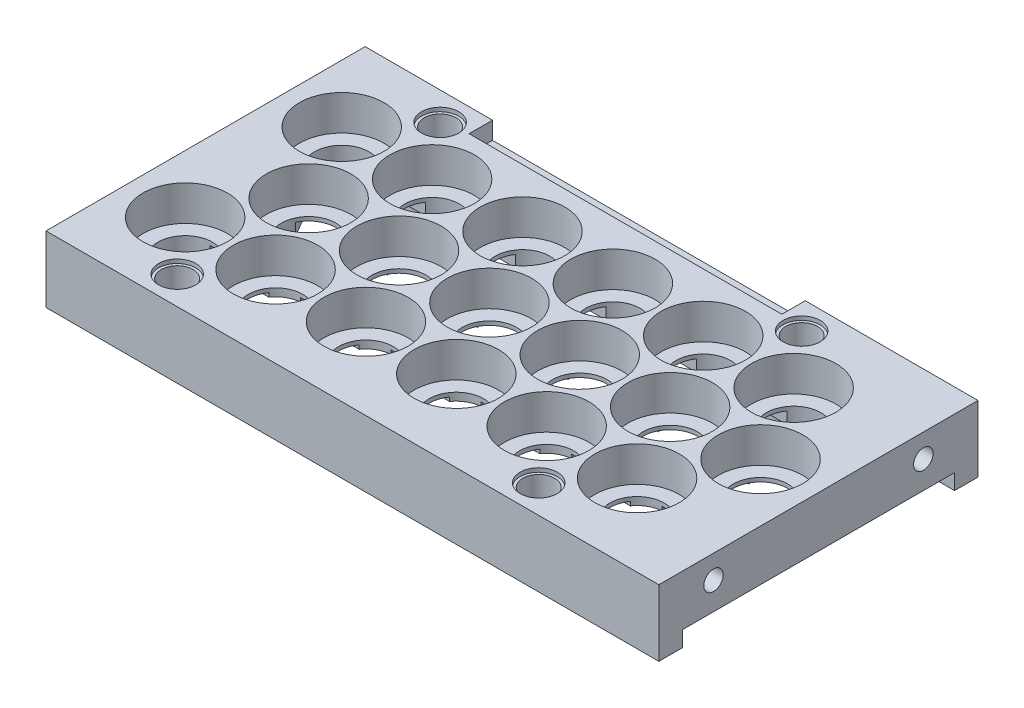
SolidWorks part; units mm, degrees
ref_plane "Front Plane" through (0, 0, 0) normal (0, 0, 1) x (1, 0, 0)
ref_plane "Top Plane" through (0, 0, 0) normal (0, 1, 0) x (1, 0, 0)
ref_plane "Right Plane" through (0, 0, 0) normal (1, 0, 0) x (0, 0, -1)
sketch "Sketch1" plane through (0, 0, 0) normal (0, 1, 0) x (1, 0, 0)
  line L0 (0, 0) -> (11.575, -20.0485) construction
  line L1 (11.575, -20.0485) -> (0, -40.097) construction
  line L2 (0, 0) -> (11.575, 0) construction
  line L3 (11.575, 0) -> (11.575, -20.0485) construction
  line L4 (11.575, -20.0485) -> (11.575, -40.097) construction
  line L5 (11.575, -40.097) -> (0, -40.097) construction
  line L6 (0, 0) -> (23.15, 0) construction
  line L7 (0, 0) -> (23.15, 0) construction
  line L8 (-14.825, -60.922) -> (142.15, -60.922)
  line L9 (-14.825, -60.922) -> (-14.825, 20.825)
  line L10 (-14.825, 20.825) -> (142.15, 20.825)
  line L11 (142.15, -60.922) -> (142.15, 20.825)
  circle A0 centre (0, 0) radius 10.825
  circle A1 centre (11.575, -20.0485) radius 10.825
  circle A2 centre (0, -40.097) radius 10.825
  circle A3 centre (23.15, 0) radius 10.825
  circle A4 centre (34.725, -20.0485) radius 10.825
  circle A5 centre (23.15, -40.097) radius 10.825
  circle A6 centre (46.3, 0) radius 10.825
  circle A7 centre (57.875, -20.0485) radius 10.825
  circle A8 centre (46.3, -40.097) radius 10.825
  circle A9 centre (69.45, 0) radius 10.825
  circle A10 centre (81.025, -20.0485) radius 10.825
  circle A11 centre (69.45, -40.097) radius 10.825
  circle A12 centre (92.6, 0) radius 10.825
  circle A13 centre (104.175, -20.0485) radius 10.825
  circle A14 centre (92.6, -40.097) radius 10.825
  circle A15 centre (115.75, 0) radius 10.825
  circle A16 centre (127.325, -20.0485) radius 10.825
  circle A17 centre (115.75, -40.097) radius 10.825
  circle A18 centre (0, 0) radius 7
  circle A19 centre (11.575, -20.0485) radius 7
  circle A20 centre (0, -40.097) radius 7
  circle A21 centre (23.15, 0) radius 7
  circle A22 centre (34.725, -20.0485) radius 7
  circle A23 centre (23.15, -40.097) radius 7
  circle A24 centre (46.3, 0) radius 7
  circle A25 centre (57.875, -20.0485) radius 7
  circle A26 centre (46.3, -40.097) radius 7
  circle A27 centre (69.45, 0) radius 7
  circle A28 centre (81.025, -20.0485) radius 7
  circle A29 centre (69.45, -40.097) radius 7
  circle A30 centre (92.6, 0) radius 7
  circle A31 centre (104.175, -20.0485) radius 7
  circle A32 centre (92.6, -40.097) radius 7
  circle A33 centre (115.75, 0) radius 7
  circle A34 centre (127.325, -20.0485) radius 7
  circle A35 centre (115.75, -40.097) radius 7
  dimension "D3" = 21.65
  dimension "D11" = 14
  dimension "D1" = 60
  dimension "D2" = 60
  dimension "D4" = 1.5
  dimension "D6" = 23.15
  dimension "D7" = 4
  dimension "D8" = 4
  dimension "D9" = 10
  dimension "D10" = 10
  dimension "D13" = 23.15
  dimension "D5" = 6
  dimension "D12" = 6
extrude "Boss-Extrude2" add sketch "Sketch1" along normal blind 11 contours L8 L11 L10 L9 A17 A16 A15 A14 A13 A12 A11 A10 A9 A8 A7 A6 A5 A4 A3 A2 A1 A0 region at (-13.0551, 0, 20.0485)
extrude "Boss-Extrude3" add sketch "Sketch1<3>" along normal blind 2 contours A0 A18 | A3 A21 | A6 A24 | A9 A27 | A12 A30 | A15 A33 | A1 A19 | A4 A22 | A7 A25 | A10 A28 | A13 A31 | A16 A34 | A17 A35 | A14 A32 | A11 A29 | A8 A26 | A5 A23 | A2 A20 region at (-10.5188, 0, 0) region at (1.0562, 0, 20.0485) region at (-10.5188, 0, 40.097) region at (12.6312, 0, 0) region at (24.2062, 0, 20.0485) region at (12.6312, 0, 40.097) region at (35.7812, 0, 0) region at (47.3562, 0, 20.0485) region at (35.7812, 0, 40.097) region at (58.9312, 0, 0) region at (70.5062, 0, 20.0485) region at (58.9312, 0, 40.097) region at (82.0812, 0, 0) region at (93.6562, 0, 20.0485) region at (82.0812, 0, 40.097) region at (105.2312, 0, 0) region at (116.8062, 0, 20.0485) region at (105.2312, 0, 40.097)
sketch "Sketch1<3>" plane through (0, 0, 0) normal (0, 1, 0) x (1, 0, 0) same geometry as "Sketch1"
sketch "Sketch2" plane through (0, 0, 0) normal (0, -1, 0) x (1, 0, 0)
  line L0 (0, 40.097) -> (11.575, 20.0485) construction
  line L1 (3.4641, 42.097) -> (15.0391, 22.0485)
  line L2 (-3.4641, 38.097) -> (8.1109, 18.0485)
  line L3 (11.575, 20.0485) -> (0, 0) construction
  line L4 (15.0391, 18.0485) -> (3.4641, -2)
  line L5 (8.1109, 22.0485) -> (-3.4641, 2)
  line L6 (19.6859, 38.097) -> (31.2609, 18.0485)
  line L7 (26.6141, 42.097) -> (38.1891, 22.0485)
  line L8 (31.2609, 22.0485) -> (19.6859, 2)
  line L9 (38.1891, 18.0485) -> (26.6141, -2)
  line L10 (23.15, 40.097) -> (34.725, 20.0485) construction
  line L11 (34.725, 20.0485) -> (23.15, 0) construction
  line L12 (42.8359, 38.097) -> (54.4109, 18.0485)
  line L13 (49.7641, 42.097) -> (61.3391, 22.0485)
  line L14 (54.4109, 22.0485) -> (42.8359, 2)
  line L15 (61.3391, 18.0485) -> (49.7641, -2)
  line L16 (46.3, 40.097) -> (57.875, 20.0485) construction
  line L17 (57.875, 20.0485) -> (46.3, 0) construction
  line L18 (65.9859, 38.097) -> (77.5609, 18.0485)
  line L19 (72.9141, 42.097) -> (84.4891, 22.0485)
  line L20 (77.5609, 22.0485) -> (65.9859, 2)
  line L21 (84.4891, 18.0485) -> (72.9141, -2)
  line L22 (69.45, 40.097) -> (81.025, 20.0485) construction
  line L23 (81.025, 20.0485) -> (69.45, 0) construction
  line L24 (89.1359, 38.097) -> (100.7109, 18.0485)
  line L25 (96.0641, 42.097) -> (107.6391, 22.0485)
  line L26 (100.7109, 22.0485) -> (89.1359, 2)
  line L27 (107.6391, 18.0485) -> (96.0641, -2)
  line L28 (92.6, 40.097) -> (104.175, 20.0485) construction
  line L29 (104.175, 20.0485) -> (92.6, 0) construction
  line L30 (112.2859, 38.097) -> (123.8609, 18.0485)
  line L31 (119.2141, 42.097) -> (130.7891, 22.0485)
  line L32 (123.8609, 22.0485) -> (112.2859, 2)
  line L33 (130.7891, 18.0485) -> (119.2141, -2)
  line L34 (115.75, 40.097) -> (127.325, 20.0485) construction
  line L35 (127.325, 20.0485) -> (115.75, 0) construction
  line L36 (-3.4641, 38.097) -> (19.6859, 38.097) construction
  line L37 (0, 40.097) -> (115.75, 40.097) construction
  line L38 (0, 44.097) -> (115.75, 44.097)
  line L39 (0, 36.097) -> (115.75, 36.097)
  line L40 (11.575, 20.0485) -> (127.325, 20.0485) construction
  line L41 (11.575, 24.0485) -> (127.325, 24.0485)
  line L42 (11.575, 16.0485) -> (127.325, 16.0485)
  line L43 (0, 0) -> (115.75, 0) construction
  line L44 (0, 4) -> (115.75, 4)
  line L45 (0, -4) -> (115.75, -4)
  arc A0 (3.4641, 42.097) -> (-3.4641, 38.097) centre (0, 40.097) ccw
  arc A1 (8.1109, 18.0485) -> (15.0391, 22.0485) centre (11.575, 20.0485) ccw
  arc A2 (15.0391, 18.0485) -> (8.1109, 22.0485) centre (11.575, 20.0485) ccw
  arc A3 (-3.4641, 2) -> (3.4641, -2) centre (0, 0) ccw
  arc A4 (26.6141, 42.097) -> (19.6859, 38.097) centre (23.15, 40.097) ccw
  arc A5 (31.2609, 18.0485) -> (38.1891, 22.0485) centre (34.725, 20.0485) ccw
  arc A6 (38.1891, 18.0485) -> (31.2609, 22.0485) centre (34.725, 20.0485) ccw
  arc A7 (19.6859, 2) -> (26.6141, -2) centre (23.15, 0) ccw
  arc A8 (49.7641, 42.097) -> (42.8359, 38.097) centre (46.3, 40.097) ccw
  arc A9 (54.4109, 18.0485) -> (61.3391, 22.0485) centre (57.875, 20.0485) ccw
  arc A10 (61.3391, 18.0485) -> (54.4109, 22.0485) centre (57.875, 20.0485) ccw
  arc A11 (42.8359, 2) -> (49.7641, -2) centre (46.3, 0) ccw
  arc A12 (72.9141, 42.097) -> (65.9859, 38.097) centre (69.45, 40.097) ccw
  arc A13 (77.5609, 18.0485) -> (84.4891, 22.0485) centre (81.025, 20.0485) ccw
  arc A14 (84.4891, 18.0485) -> (77.5609, 22.0485) centre (81.025, 20.0485) ccw
  arc A15 (65.9859, 2) -> (72.9141, -2) centre (69.45, 0) ccw
  arc A16 (96.0641, 42.097) -> (89.1359, 38.097) centre (92.6, 40.097) ccw
  arc A17 (100.7109, 18.0485) -> (107.6391, 22.0485) centre (104.175, 20.0485) ccw
  arc A18 (107.6391, 18.0485) -> (100.7109, 22.0485) centre (104.175, 20.0485) ccw
  arc A19 (89.1359, 2) -> (96.0641, -2) centre (92.6, 0) ccw
  arc A20 (119.2141, 42.097) -> (112.2859, 38.097) centre (115.75, 40.097) ccw
  arc A21 (123.8609, 18.0485) -> (130.7891, 22.0485) centre (127.325, 20.0485) ccw
  arc A22 (130.7891, 18.0485) -> (123.8609, 22.0485) centre (127.325, 20.0485) ccw
  arc A23 (112.2859, 2) -> (119.2141, -2) centre (115.75, 0) ccw
  arc A24 (0, 44.097) -> (0, 36.097) centre (0, 40.097) ccw
  arc A25 (115.75, 36.097) -> (115.75, 44.097) centre (115.75, 40.097) ccw
  arc A26 (11.575, 24.0485) -> (11.575, 16.0485) centre (11.575, 20.0485) ccw
  arc A27 (127.325, 16.0485) -> (127.325, 24.0485) centre (127.325, 20.0485) ccw
  arc A28 (0, 4) -> (0, -4) centre (0, 0) ccw
  arc A29 (115.75, -4) -> (115.75, 4) centre (115.75, 0) ccw
  point P3 (5.7875, 30.0727)
  point P8 (5.7875, 10.0242)
  point P18 (28.9375, 30.0727)
  point P25 (28.9375, 10.0242)
  point P34 (52.0875, 30.0727)
  point P39 (52.0875, 10.0242)
  point P48 (75.2375, 30.0727)
  point P53 (75.2375, 10.0242)
  point P62 (98.3875, 30.0727)
  point P67 (98.3875, 10.0242)
  point P76 (121.5375, 30.0727)
  point P81 (121.5375, 10.0242)
  point P91 (57.875, 40.097)
  point P96 (69.45, 20.0485)
  point P103 (57.875, 0)
  circle M62 centre (0, 0) radius 7
  circle M63 centre (23.15, 0) radius 7
  circle M64 centre (46.3, 0) radius 7
  circle M65 centre (69.45, 0) radius 7
  circle M66 centre (92.6, 0) radius 7
  circle M67 centre (115.75, 0) radius 7
  circle M68 centre (11.575, 20.0485) radius 7
  circle M69 centre (34.725, 20.0485) radius 7
  circle M70 centre (57.875, 20.0485) radius 7
  circle M71 centre (81.025, 20.0485) radius 7
  circle M72 centre (104.175, 20.0485) radius 7
  circle M73 centre (127.325, 20.0485) radius 7
  circle M74 centre (115.75, 40.097) radius 7
  circle M75 centre (92.6, 40.097) radius 7
  circle M76 centre (69.45, 40.097) radius 7
  circle M77 centre (46.3, 40.097) radius 7
  circle M78 centre (23.15, 40.097) radius 7
  circle M79 centre (0, 40.097) radius 7
  dimension "D1" = 8
  dimension "D3" = 23.15
  dimension "D4" = 8
  dimension "D5" = 8
  dimension "D6" = 8
extrude "Cut-Extrude1" cut sketch "Sketch2" against normal blind 1 contours L1 L39 L38 M78 M79 | L7 L39 L38 M77 M78 | L39 L2 L1 M79 M68 | L42 L8 L6 L41 M68 M69 | L6 L41 L7 L39 M69 M78 | L12 L41 L13 L39 M70 M77 | L13 L39 L38 M76 M77 | L18 L41 L19 L39 M71 M76 | L19 L39 L38 M75 M76 | L24 L41 L25 L39 M72 M75 | L25 L39 L38 M74 M75 | L30 L41 L31 M73 M74 | L42 L32 L30 L41 M72 M73 | L42 L26 L24 L41 M71 M72 | L42 L20 L18 L41 M70 M71 | L42 L14 L12 L41 M69 M70 | L45 L44 L4 M62 M63 | L44 L4 L5 M62 M68 | L45 L44 L9 M63 M64 | L45 L44 L15 M64 M65 | L45 L44 L21 M65 M66 | L45 L44 L27 M66 M67 | L44 L27 L42 L26 M66 M72 | L42 L32 L33 M67 M73 | L44 L21 L42 L20 M65 M71 | L44 L15 L42 L14 M64 M70 | L39 L13 M77 | L39 L25 M75 | L39 L19 M76 | L41 L6 M69 | L44 L4 M62 | L44 L15 M64 | L44 L21 M65 | L44 L27 M66 | L41 L30 M73 | L32 L42 M73 | L41 L24 M72 | L26 L42 M72 | L41 L18 M71 | L20 L42 M71 | L41 L12 M70 | L14 L42 M70 | L44 L9 L42 L8 M63 M69 | L8 L42 M69 | L39 L7 M78 | L39 L1 M79 | L44 A29 L45 A28 region at (11.6138, 0, 40.1242) region at (6.3461, 0, 36.4331) region at (5.7834, 0, 30.0255) region at (23.0718, 0, 20.0485) region at (28.9375, 0, 30.0727) region at (34.7638, 0, 40.1242) region at (28.3789, 0, 23.7124) region at (5.7834, 0, 10.0715) region at (29.4961, 0, 36.4331) region at (57.9138, 0, 40.1242) region at (28.3789, 0, 16.3846) region at (28.9375, 0, 10.0242) region at (6.3461, 0, 3.6639) region at (11.6138, 0, -0.0272) region at (52.0875, 0, 30.0727) region at (46.2218, 0, 20.0485) region at (52.6461, 0, 36.4331) region at (81.0638, 0, 40.1242) region at (51.5289, 0, 23.7124) region at (34.7638, 0, -0.0272) region at (75.2375, 0, 30.0727) region at (75.7961, 0, 36.4331) region at (104.2138, 0, 40.1242) region at (74.6789, 0, 23.7124) region at (69.3718, 0, 20.0485) region at (51.5289, 0, 16.3846) region at (52.0875, 0, 10.0242) region at (57.9138, 0, -0.0272) region at (98.3875, 0, 30.0727) region at (98.9461, 0, 36.4331) region at (97.8289, 0, 23.7124) region at (92.5218, 0, 20.0485) region at (74.6789, 0, 16.3846) region at (52.6461, 0, 3.6639) region at (81.0638, 0, -0.0272) region at (121.5416, 0, 30.12) region at (75.2375, 0, 10.0242) region at (120.9789, 0, 23.7124) region at (115.6718, 0, 20.0485) region at (97.8289, 0, 16.3846) region at (75.7961, 0, 3.6639) region at (104.2138, 0, -0.0272) region at (98.3875, 0, 10.0242) region at (121.5416, 0, 9.977) region at (120.9789, 0, 16.3846) region at (98.9461, 0, 3.6639)
sketch "Sketch9" plane through (0, 11, 0) normal (0, 1, 0) x (1, 0, 0)
  line L0 (11.575, -60.922) -> (11.575, 20.825)
  line L1 (-14.825, 20.825) -> (142.15, 20.825) construction
  line L2 (104.175, 20.825) -> (104.175, -60.922)
  line L3 (-14.825, -60.922) -> (142.15, -60.922) construction
  circle A0 centre (11.575, 13.625) radius 4.0767
  circle A1 centre (11.575, -53.722) radius 4.0767
  circle A2 centre (104.175, -53.722) radius 4.0767
  circle A3 centre (104.175, 13.625) radius 4.0767
  point P0 (11.575, 13.625)
  point P7 (11.575, -20.0485)
  point P15 (104.175, -20.0485)
  point P20 (104.175, 13.625)
  point P21 (104.175, -53.722)
  point P22 (11.575, -53.722)
  dimension "D5" = 8.1534
  dimension "D1" = 7.2
  dimension "D4" = 7.2
extrude "Cut-Extrude3" cut sketch "Sketch9" against normal up to next contours A2 | A1 | A0 | A3
sketch "Sketch10" plane through (0, 11, 0) normal (0, 1, 0) x (1, 0, 0)
  circle A0 centre (11.575, 13.625) radius 4.7625
  circle A1 centre (104.175, 13.625) radius 4.7625
  circle A2 centre (104.175, -53.722) radius 4.7625
  circle A3 centre (11.575, -53.722) radius 4.7625
  dimension "D1" = 9.525
extrude "Cut-Extrude4" cut sketch "Sketch10" against normal blind 1
sketch "Sketch13" plane through (0, 0, 0) normal (0, -1, 0) x (1, 0, 0)
  line L0 (142.15, 60.922) -> (142.15, -20.825) construction
  line L5 (3.575, 53.722) -> (3.575, 60.922)
  line L8 (-14.825, 60.922) -> (142.15, 60.922) construction
  line L9 (3.575, 60.922) -> (19.575, 60.922)
  line L10 (19.575, 60.922) -> (19.575, 53.722)
  line L12 (57.875, 20.0485) -> (57.875, -20.825) construction
  line L13 (-14.825, -20.825) -> (142.15, -20.825) construction
  line L14 (11.575, 20.0485) -> (127.325, 20.0485) construction
  line L16 (96.175, 60.922) -> (96.175, 53.722)
  line L17 (112.175, 60.922) -> (96.175, 60.922)
  line L18 (112.175, 53.722) -> (112.175, 60.922)
  line L19 (-14.825, 60.922) -> (142.15, 60.922)
  line L20 (-14.825, 60.922) -> (-14.825, 54.922)
  line L21 (-14.825, 54.922) -> (142.15, 54.922)
  line L22 (142.15, 60.922) -> (142.15, 54.922)
  line L23 (142.15, -20.825) -> (142.15, -14.825)
  line L24 (-14.825, -14.825) -> (142.15, -14.825)
  line L25 (-14.825, -20.825) -> (-14.825, -14.825)
  line L26 (-14.825, -20.825) -> (142.15, -20.825)
  line L27 (112.175, -13.625) -> (112.175, -20.825)
  line L28 (112.175, -20.825) -> (96.175, -20.825)
  line L29 (96.175, -20.825) -> (96.175, -13.625)
  line L32 (19.575, -20.825) -> (19.575, -13.625)
  line L33 (3.575, -20.825) -> (19.575, -20.825)
  line L34 (3.575, -13.625) -> (3.575, -20.825)
  circle A4 centre (11.575, 53.722) radius 6.5
  circle A5 centre (11.575, 53.722) radius 8
  circle A6 centre (104.175, 53.722) radius 8
  circle A7 centre (104.175, 53.722) radius 6.5
  circle A8 centre (104.175, -13.625) radius 6.5
  circle A9 centre (104.175, -13.625) radius 8
  circle A10 centre (11.575, -13.625) radius 8
  circle A11 centre (11.575, -13.625) radius 6.5
  line M15 (142.15, 60.922) -> (-14.825, 60.922)
  line M16 (-14.825, 60.922) -> (-14.825, -20.825)
  line M17 (-14.825, -20.825) -> (142.15, -20.825)
  line M18 (142.15, -20.825) -> (142.15, 60.922)
  dimension "D1" = 13
  dimension "D2" = 16
  dimension "D3" = 6
extrude "Boss-Extrude7" add sketch "Sketch13" along normal blind 6 contours L21 L5 M16 M15 | A5 L5 L21 M15 | A5 L21 L10 M15 | L10 L21 L16 M15 | L21 A5 L19 A4 | A5 L21 A4 | L21 A6 L16 M15 | L21 A7 A6 L19 | L21 A7 A6 | A6 L21 L18 M15 | L18 L21 M18 M15 | A9 L24 L29 L26 | L28 A9 L24 A8 | A9 L26 L27 L24 | L24 L27 L26 M18 | L32 L26 L29 L24 | L24 A9 A8 | L34 L24 M16 M17 | L26 A10 L24 L34 | L24 A11 A10 | L24 A11 A10 L33 | L24 A10 L26 L32 region at (3.7817, 0, 54.3098) region at (-5.625, 0, 57.922) region at (4.8282, 0, 59.2567) region at (5.2714, 0, 58.3681) region at (18.3218, 0, 59.2567) region at (57.875, 0, 57.922) region at (-5.625, 0, -17.825) region at (97.4282, 0, 59.2567) region at (4.8282, 0, -19.1597) region at (96.3817, 0, 54.3098) region at (97.8714, 0, 58.3681) region at (3.7817, 0, -14.2128) region at (4.4261, 0, -14.9942) region at (110.9218, 0, 59.2567) region at (127.1625, 0, 57.922) region at (18.3218, 0, -19.1597) region at (57.875, 0, -17.825) region at (97.4282, 0, -19.1597) region at (127.1625, 0, -17.825) region at (96.3817, 0, -14.2128) region at (97.0261, 0, -14.9942) region at (110.9218, 0, -19.1597)
sketch "Sketch14" plane through (0, 0, 0) normal (0, -1, 0) x (1, 0, 0)
  line L2 (142.15, 54.922) -> (142.15, -14.825) construction
  line L4 (5.2386, 17.0736) -> (-0.5918, 6.9749) construction
  line L5 (5.7446, -4) -> (17.4054, -4) construction
  line L6 (28.8946, -4) -> (40.5554, -4) construction
  line L7 (52.0446, -4) -> (63.7054, -4) construction
  line L8 (75.1946, -4) -> (86.8554, -4) construction
  line L9 (98.3446, -4) -> (110.0054, -4) construction
  line L10 (127.9168, 13.0736) -> (122.0864, 2.9749) construction
  line L11 (122.0864, 37.122) -> (127.9168, 27.0234) construction
  line L12 (98.3446, 44.097) -> (110.0054, 44.097) construction
  line L13 (75.1946, 44.097) -> (86.8554, 44.097) construction
  line L14 (52.0446, 44.097) -> (63.7054, 44.097) construction
  line L15 (28.8946, 44.097) -> (40.5554, 44.097) construction
  line L16 (-0.5918, 33.122) -> (5.2386, 23.0234) construction
  line L17 (5.7446, 44.097) -> (17.4054, 44.097) construction
  line L20 (142.15, 54.922) -> (142.15, -14.825)
  line L22 (5.2386, 17.0736) -> (-0.5918, 6.9749)
  line L23 (5.7446, -4) -> (17.4054, -4)
  line L24 (28.8946, -4) -> (40.5554, -4)
  line L25 (52.0446, -4) -> (63.7054, -4)
  line L26 (75.1946, -4) -> (86.8554, -4)
  line L27 (98.3446, -4) -> (110.0054, -4)
  line L28 (127.9168, 13.0736) -> (122.0864, 2.9749)
  line L29 (122.0864, 37.122) -> (127.9168, 27.0234)
  line L30 (98.3446, 44.097) -> (110.0054, 44.097)
  line L31 (75.1946, 44.097) -> (86.8554, 44.097)
  line L32 (52.0446, 44.097) -> (63.7054, 44.097)
  line L33 (28.8946, 44.097) -> (40.5554, 44.097)
  line L34 (-0.5918, 33.122) -> (5.2386, 23.0234)
  line L35 (5.7446, 44.097) -> (17.4054, 44.097)
  line L36 (112.0845, -14.825) -> (142.15, -14.825) construction
  line L37 (19.4845, -14.825) -> (96.2655, -14.825) construction
  line L38 (-14.825, -14.825) -> (3.6655, -14.825) construction
  line L39 (-14.825, 54.922) -> (-14.825, -14.825) construction
  line L40 (112.0845, 54.922) -> (142.15, 54.922) construction
  line L41 (19.4845, 54.922) -> (96.2655, 54.922) construction
  line L42 (-14.825, 54.922) -> (3.6655, 54.922) construction
  line L43 (112.0845, -14.825) -> (142.15, -14.825)
  line L44 (19.4845, -14.825) -> (96.2655, -14.825)
  line L45 (-14.825, -14.825) -> (3.6655, -14.825)
  line L46 (-14.825, 54.922) -> (-14.825, -14.825)
  line L47 (112.0845, 54.922) -> (142.15, 54.922)
  line L48 (19.4845, 54.922) -> (96.2655, 54.922)
  line L49 (-14.825, 54.922) -> (3.6655, 54.922)
  arc A3 (5.2386, 23.0234) -> (5.2386, 17.0736) centre (11.575, 20.0485) ccw construction
  arc A4 (-0.5918, 6.9749) -> (5.7446, -4) centre (0, 0) ccw construction
  arc A5 (17.4054, -4) -> (28.8946, -4) centre (23.15, 0) ccw construction
  arc A6 (40.5554, -4) -> (52.0446, -4) centre (46.3, 0) ccw construction
  arc A7 (63.7054, -4) -> (75.1946, -4) centre (69.45, 0) ccw construction
  arc A8 (86.8554, -4) -> (98.3446, -4) centre (92.6, 0) ccw construction
  arc A9 (110.0054, -4) -> (122.0864, 2.9749) centre (115.75, 0) ccw construction
  arc A10 (127.9168, 13.0736) -> (127.9168, 27.0234) centre (127.325, 20.0485) ccw construction
  arc A11 (122.0864, 37.122) -> (110.0054, 44.097) centre (115.75, 40.097) ccw construction
  arc A12 (98.3446, 44.097) -> (86.8554, 44.097) centre (92.6, 40.097) ccw construction
  arc A13 (75.1946, 44.097) -> (63.7054, 44.097) centre (69.45, 40.097) ccw construction
  arc A14 (52.0446, 44.097) -> (40.5554, 44.097) centre (46.3, 40.097) ccw construction
  arc A16 (28.8946, 44.097) -> (17.4054, 44.097) centre (23.15, 40.097) ccw construction
  arc A17 (5.7446, 44.097) -> (-0.5918, 33.122) centre (0, 40.097) ccw construction
  arc A21 (5.2386, 23.0234) -> (5.2386, 17.0736) centre (11.575, 20.0485) ccw
  arc A22 (-0.5918, 6.9749) -> (5.7446, -4) centre (0, 0) ccw
  arc A23 (17.4054, -4) -> (28.8946, -4) centre (23.15, 0) ccw
  arc A24 (40.5554, -4) -> (52.0446, -4) centre (46.3, 0) ccw
  arc A25 (63.7054, -4) -> (75.1946, -4) centre (69.45, 0) ccw
  arc A26 (86.8554, -4) -> (98.3446, -4) centre (92.6, 0) ccw
  arc A27 (110.0054, -4) -> (122.0864, 2.9749) centre (115.75, 0) ccw
  arc A28 (127.9168, 13.0736) -> (127.9168, 27.0234) centre (127.325, 20.0485) ccw
  arc A29 (122.0864, 37.122) -> (110.0054, 44.097) centre (115.75, 40.097) ccw
  arc A30 (98.3446, 44.097) -> (86.8554, 44.097) centre (92.6, 40.097) ccw
  arc A31 (75.1946, 44.097) -> (63.7054, 44.097) centre (69.45, 40.097) ccw
  arc A32 (52.0446, 44.097) -> (40.5554, 44.097) centre (46.3, 40.097) ccw
  arc A34 (28.8946, 44.097) -> (17.4054, 44.097) centre (23.15, 40.097) ccw
  arc A35 (5.7446, 44.097) -> (-0.5918, 33.122) centre (0, 40.097) ccw
  arc A36 (112.0845, -14.825) -> (96.2655, -14.825) centre (104.175, -13.625) ccw construction
  arc A37 (19.4845, -14.825) -> (3.6655, -14.825) centre (11.575, -13.625) ccw construction
  arc A38 (96.2655, 54.922) -> (112.0845, 54.922) centre (104.175, 53.722) ccw construction
  arc A39 (3.6655, 54.922) -> (19.4845, 54.922) centre (11.575, 53.722) ccw construction
  arc A40 (112.0845, -14.825) -> (96.2655, -14.825) centre (104.175, -13.625) ccw
  arc A41 (19.4845, -14.825) -> (3.6655, -14.825) centre (11.575, -13.625) ccw
  arc A42 (96.2655, 54.922) -> (112.0845, 54.922) centre (104.175, 53.722) ccw
  arc A43 (3.6655, 54.922) -> (19.4845, 54.922) centre (11.575, 53.722) ccw
extrude "Boss-Extrude9" add sketch "Sketch14" along normal blind 2
sketch "Sketch16" plane through (0, 0, 0) normal (0, -1, 0) x (1, 0, 0)
  line L0 (17.4054, 36.097) -> (12.1668, 27.0234) construction
  line L1 (12.1668, 27.0234) -> (17.3196, 24.0485) construction
  line L2 (17.3196, 24.0485) -> (22.5582, 33.122) construction
  line L3 (22.5582, 33.122) -> (17.4054, 36.097) construction
  line L4 (14.7861, 31.5602) -> (19.9389, 28.5853) construction
  line L5 (15.5361, 32.8592) -> (20.6889, 29.8843)
  line L6 (14.0361, 30.2612) -> (19.1889, 27.2862)
  line L7 (11.575, 20.0485) -> (126.446, 20.0485) construction
  line L8 (40.5554, 36.097) -> (35.3168, 27.0234) construction
  line L9 (35.3168, 27.0234) -> (40.4696, 24.0485) construction
  line L10 (40.4696, 24.0485) -> (45.7082, 33.122) construction
  line L11 (45.7082, 33.122) -> (40.5554, 36.097) construction
  line L12 (37.9361, 31.5602) -> (43.0889, 28.5853) construction
  line L13 (38.6861, 32.8592) -> (43.8389, 29.8843)
  line L14 (37.1861, 30.2612) -> (42.3389, 27.2862)
  line L15 (63.7054, 36.097) -> (58.4668, 27.0234) construction
  line L16 (58.4668, 27.0234) -> (63.6196, 24.0485) construction
  line L17 (63.6196, 24.0485) -> (68.8582, 33.122) construction
  line L18 (68.8582, 33.122) -> (63.7054, 36.097) construction
  line L19 (61.0861, 31.5602) -> (66.2389, 28.5853) construction
  line L20 (61.8361, 32.8592) -> (66.9889, 29.8843)
  line L21 (60.3361, 30.2612) -> (65.4889, 27.2862)
  line L22 (86.8554, 36.097) -> (81.6168, 27.0234) construction
  line L23 (81.6168, 27.0234) -> (86.7696, 24.0485) construction
  line L24 (86.7696, 24.0485) -> (92.0082, 33.122) construction
  line L25 (92.0082, 33.122) -> (86.8554, 36.097) construction
  line L26 (84.2361, 31.5602) -> (89.3889, 28.5853) construction
  line L27 (84.9861, 32.8592) -> (90.1389, 29.8843)
  line L28 (83.4861, 30.2612) -> (88.6389, 27.2862)
  line L29 (110.0054, 36.097) -> (104.7668, 27.0234) construction
  line L30 (104.7668, 27.0234) -> (109.9196, 24.0485) construction
  line L31 (109.9196, 24.0485) -> (115.1582, 33.122) construction
  line L32 (115.1582, 33.122) -> (110.0054, 36.097) construction
  line L33 (107.3861, 31.5602) -> (112.5389, 28.5853) construction
  line L34 (108.1361, 32.8592) -> (113.2889, 29.8843)
  line L35 (106.6361, 30.2612) -> (111.7889, 27.2862)
  line L36 (14.7861, 8.5368) -> (19.9389, 11.5117) construction
  line L37 (15.5361, 7.2377) -> (20.6889, 10.2127)
  line L38 (14.0361, 9.8358) -> (19.1889, 12.8108)
  line L39 (37.9361, 8.5368) -> (43.0889, 11.5117) construction
  line L40 (38.6861, 7.2377) -> (43.8389, 10.2127)
  line L41 (37.1861, 9.8358) -> (42.3389, 12.8108)
  line L42 (61.0861, 8.5368) -> (66.2389, 11.5117) construction
  line L43 (61.8361, 7.2377) -> (66.9889, 10.2127)
  line L44 (60.3361, 9.8358) -> (65.4889, 12.8108)
  line L45 (84.2361, 8.5368) -> (89.3889, 11.5117) construction
  line L46 (84.9861, 7.2377) -> (90.1389, 10.2127)
  line L47 (83.4861, 9.8358) -> (88.6389, 12.8108)
  line L48 (107.3861, 8.5368) -> (112.5389, 11.5117) construction
  line L49 (108.1361, 7.2377) -> (113.2889, 10.2127)
  line L50 (106.6361, 9.8358) -> (111.7889, 12.8108)
  line L51 (115.1582, 6.9749) -> (110.0054, 4) construction
  line L52 (109.9196, 16.0485) -> (115.1582, 6.9749) construction
  line L53 (104.7668, 13.0736) -> (109.9196, 16.0485) construction
  line L54 (110.0054, 4) -> (104.7668, 13.0736) construction
  line L55 (92.0082, 6.9749) -> (86.8554, 4) construction
  line L56 (86.7696, 16.0485) -> (92.0082, 6.9749) construction
  line L57 (81.6168, 13.0736) -> (86.7696, 16.0485) construction
  line L58 (86.8554, 4) -> (81.6168, 13.0736) construction
  line L59 (68.8582, 6.9749) -> (63.7054, 4) construction
  line L60 (63.6196, 16.0485) -> (68.8582, 6.9749) construction
  line L61 (58.4668, 13.0736) -> (63.6196, 16.0485) construction
  line L62 (63.7054, 4) -> (58.4668, 13.0736) construction
  line L63 (45.7082, 6.9749) -> (40.5554, 4) construction
  line L64 (40.4696, 16.0485) -> (45.7082, 6.9749) construction
  line L65 (35.3168, 13.0736) -> (40.4696, 16.0485) construction
  line L66 (40.5554, 4) -> (35.3168, 13.0736) construction
  line L67 (22.5582, 6.9749) -> (17.4054, 4) construction
  line L68 (17.3196, 16.0485) -> (22.5582, 6.9749) construction
  line L69 (12.1668, 13.0736) -> (17.3196, 16.0485) construction
  line L70 (17.4054, 4) -> (12.1668, 13.0736) construction
  arc A0 (15.5361, 32.8592) -> (14.0361, 30.2612) centre (14.7861, 31.5602) ccw
  arc A1 (19.1889, 27.2862) -> (20.6889, 29.8843) centre (19.9389, 28.5853) ccw
  arc A2 (38.6861, 32.8592) -> (37.1861, 30.2612) centre (37.9361, 31.5602) ccw
  arc A3 (42.3389, 27.2862) -> (43.8389, 29.8843) centre (43.0889, 28.5853) ccw
  arc A4 (61.8361, 32.8592) -> (60.3361, 30.2612) centre (61.0861, 31.5602) ccw
  arc A5 (65.4889, 27.2862) -> (66.9889, 29.8843) centre (66.2389, 28.5853) ccw
  arc A6 (84.9861, 32.8592) -> (83.4861, 30.2612) centre (84.2361, 31.5602) ccw
  arc A7 (88.6389, 27.2862) -> (90.1389, 29.8843) centre (89.3889, 28.5853) ccw
  arc A8 (108.1361, 32.8592) -> (106.6361, 30.2612) centre (107.3861, 31.5602) ccw
  arc A9 (111.7889, 27.2862) -> (113.2889, 29.8843) centre (112.5389, 28.5853) ccw
  arc A10 (40.5554, 36.097) -> (45.7082, 33.122) centre (46.3, 40.097) ccw construction
  arc A11 (15.5361, 7.2377) -> (14.0361, 9.8358) centre (14.7861, 8.5368) cw
  arc A12 (19.1889, 12.8108) -> (20.6889, 10.2127) centre (19.9389, 11.5117) cw
  arc A13 (38.6861, 7.2377) -> (37.1861, 9.8358) centre (37.9361, 8.5368) cw
  arc A14 (42.3389, 12.8108) -> (43.8389, 10.2127) centre (43.0889, 11.5117) cw
  arc A15 (61.8361, 7.2377) -> (60.3361, 9.8358) centre (61.0861, 8.5368) cw
  arc A16 (65.4889, 12.8108) -> (66.9889, 10.2127) centre (66.2389, 11.5117) cw
  arc A17 (84.9861, 7.2377) -> (83.4861, 9.8358) centre (84.2361, 8.5368) cw
  arc A18 (88.6389, 12.8108) -> (90.1389, 10.2127) centre (89.3889, 11.5117) cw
  arc A19 (108.1361, 7.2377) -> (106.6361, 9.8358) centre (107.3861, 8.5368) cw
  arc A20 (111.7889, 12.8108) -> (113.2889, 10.2127) centre (112.5389, 11.5117) cw
  point P10 (17.3625, 30.0727)
  point P25 (40.5125, 30.0727)
  point P36 (63.6625, 30.0727)
  point P47 (86.8125, 30.0727)
  point P58 (109.9625, 30.0727)
  point P68 (17.3625, 10.0242)
  point P75 (40.5125, 10.0242)
  point P82 (63.6625, 10.0242)
  point P89 (86.8125, 10.0242)
  point P96 (109.9625, 10.0242)
  dimension "D1" = 1.5
  dimension "D2" = 5
extrude "Boss-Extrude10" add sketch "Sketch16" along normal blind 2
sketch "Sketch17" plane through (0, -2, 0) normal (0, -1, 0) x (-1, 0, 0)
  line L0 (-57.875, -44.097) -> (-57.875, -54.922) construction
  line L1 (-63.7054, -44.097) -> (-52.0446, -44.097) construction
  line L2 (-19.4845, -54.922) -> (-96.2655, -54.922) construction
  line L3 (-142.15, 14.825) -> (-142.15, -54.922) construction
  line L4 (14.825, -54.922) -> (14.825, 14.825) construction
  line L5 (10.825, -49.5095) -> (-57.875, -49.5095) construction
  line L6 (-57.875, -49.5095) -> (-132.15, -49.5095) construction
  line L7 (-127.325, -20.0485) -> (-11.575, -20.0485)
  line L8 (-57.875, 9.4125) -> (-132.15, 9.4125) construction
  line L9 (10.825, 9.4125) -> (-57.875, 9.4125) construction
  line L10 (-57.875, 4) -> (-57.875, 14.825) construction
  circle A0 centre (10.825, -49.5095) radius 2
  circle A1 centre (-57.875, -49.5095) radius 2
  circle A2 centre (-132.15, -49.5095) radius 2
  circle A3 centre (-132.15, 9.4125) radius 2
  circle A4 centre (-57.875, 9.4125) radius 2
  circle A5 centre (10.825, 9.4125) radius 2
  dimension "D1" = 4
  dimension "D2" = 10
  dimension "D3" = 4
extrude "Cut-Extrude5" cut sketch "Sketch17" against normal blind 4 contours A3 | A2 | A4 | A5 | A0 | A1 region at (-10.825, -2, 49.5095) region at (57.875, -2, 49.5095) region at (132.15, -2, 49.5095) region at (132.15, -2, -9.4125) region at (57.875, -2, -9.4125) region at (-10.825, -2, -9.4125)
sketch "Sketch18" plane through (0, 0, -20.825) normal (0, 0, -1) x (-1, 0, 0)
  line L1 (-97.9, 11) -> (-17.8, 11)
  line L2 (-97.9, 11) -> (-17.8, 11)
  line L3 (-97.9, 11) -> (-97.9, 6.525)
  line L4 (-17.8, 11) -> (-17.8, 6.525)
  line L5 (-97.9, 6.525) -> (-17.8, 6.525)
  line L6 (-104.15, 11) -> (-11.55, 11)
  line L7 (14.825, 11) -> (-142.15, 11) construction
  point P7 (-57.85, 11)
  point P10 (-57.85, 11)
  line M8 (14.825, 11) -> (-142.15, 11)
  dimension "D1" = 80.1
  dimension "D2" = 4.475
  dimension "D3" = 92.6
  dimension "D4" = 38
extrude "Cut-Extrude6" cut sketch "Sketch18" against normal blind 6 contours L3 L5 L4 M8 region at (57.85, 8.7625, -20.825)
sketch "Sketch19" plane through (0, 0, -20.825) normal (0, 0, -1) x (-1, 0, 0)
  line L0 (-85.9, 6.525) -> (-29.8, 6.525)
  line L1 (-85.9, 6.525) -> (-85.9, 0.2625)
  line L2 (-29.8, 6.525) -> (-29.8, 0.2625)
  line L3 (-85.9, 0.2625) -> (-29.8, 0.2625)
  line L4 (-97.9, 6.525) -> (-17.8, 6.525) construction
  line L5 (-97.9, 6.525) -> (-17.8, 6.525) construction
  line L6 (-85.9, 6.525) -> (-97.9, 6.525) construction
  line L7 (-29.8, 6.525) -> (-17.8, 6.525) construction
  line L8 (-57.85, 6.525) -> (-57.85, -6)
  line L9 (14.825, -6) -> (-142.15, -6) construction
  circle A0 centre (-85.9, 0.2625) radius 2
  circle A1 centre (-29.8, 0.2625) radius 2
  point P17 (-57.85, 0.2625)
  dimension "D2" = 4
  dimension "D1" = 12
extrude "Cut-Extrude7" cut sketch "Sketch19" against normal blind 5 contours L1 A0 L3 | L3 A0 L1 | L3 A1 L2 | L2 A1 L3 region at (85.0512, 1.1113, -20.825) region at (86.1829, -0.0204, -20.825) region at (29.5171, -0.0204, -20.825) region at (30.6488, 1.1113, -20.825)
sketch "Sketch20" plane through (142.15, 0, 0) normal (1, 0, 0) x (0, 0, -1)
  line L0 (-46.922, 5) -> (-60.922, 5)
  line L1 (6.825, 5) -> (20.825, 5)
  line L2 (-46.922, 5) -> (-46.922, 11)
  line L3 (6.825, 5) -> (6.825, 11)
  line L4 (-60.922, 11) -> (20.825, 11) construction
  line L5 (20.825, 11) -> (20.825, -6) construction
  line L6 (-60.922, 11) -> (-60.922, -6) construction
  circle A0 centre (-46.922, 5) radius 2.5
  circle A1 centre (6.825, 5) radius 2.5
  point P8 (3.1513, 11)
  point P11 (20.825, 5)
  point P14 (-44.5202, 11)
  point P15 (-60.922, 5)
  dimension "D1" = 5
  dimension "D2" = 14
  dimension "D3" = 6
extrude "Cut-Extrude8" cut sketch "Sketch20" against normal blind 10 contours L0 A0 L2 | L2 A0 L0 | A1 region at (142.15, 4.6463, 46.5683) region at (142.15, 6.061, 47.983)
equation "\"hole_diameter\"= 21.65"
equation "\"D3@Sketch1\"=\"hole_diameter\""
equation "\"cell_spacing\"= 1.5"
equation "\"D4@Sketch1\"=\"cell_spacing\""
equation "\"D6@Sketch1\"=\"hole_diameter\"+\"cell_spacing\""
equation "\"len_spacing\"= 4"
equation "\"D7@Sketch1\"=\"len_spacing\""
equation "\"D8@Sketch1\"=\"len_spacing\""
equation "\"wid_spacing\"= 10"
equation "\"D9@Sketch1\"=\"wid_spacing\""
equation "\"D10@Sketch1\"=\"wid_spacing\""
equation "\"nipple\"= 14"
equation "\"D11@Sketch1\"=\"nipple\""
equation "\"D13@Sketch1\"=\"hole_diameter\"+\"cell_spacing\""
equation "\"channel\"= 8"
equation "\"D1@Sketch2\"=\"channel\""
equation "\"D3@Sketch2\"=\"hole_diameter\"+\"cell_spacing\""
equation "\"D4@Sketch2\"=\"channel\""
equation "\"D5@Sketch2\"=\"channel\""
equation "\"D6@Sketch2\"=\"channel\""
equation "\"lip\"= 6"
equation "\"lip_height\"= 1"
equation "\"outer_fillet\"=6"
equation "\"insert_placement\"= 7.2"
equation "\"D4@Sketch9\"=\"insert_placement\""
equation "\"D1@Sketch9\"=\"insert_placement\""
equation "\"heat_insert_diameter\"=8.1534"
equation "\"D5@Sketch9\"=\"heat_insert_diameter\""
equation "\"heat_insert_lip_diameter\"=9.525"
equation "\"D1@Sketch10\"=\"heat_insert_lip_diameter\""
equation "\"bolt_head_diameter\"=13"
equation "\"D1@Sketch13\"=\"bolt_head_diameter\""
equation "\"D2@Sketch13\"=\"bolt_head_diameter\"+3"
equation "\"D3@Sketch13\"=\"lip\""
equation "\"small_heat_insert\"= 4"
equation "\"D1@Sketch17\"=\"small_heat_insert\""
equation "\"bdm_cut_depth\"=6"
equation "\"D1@Cut-Extrude6\"=\"bdm_cut_depth\""
equation "\"D2@Sketch19\"=\"small_heat_insert\""
equation "\"heat_insert_space\"=6"
equation "\"heat_insert\"=5.5"
